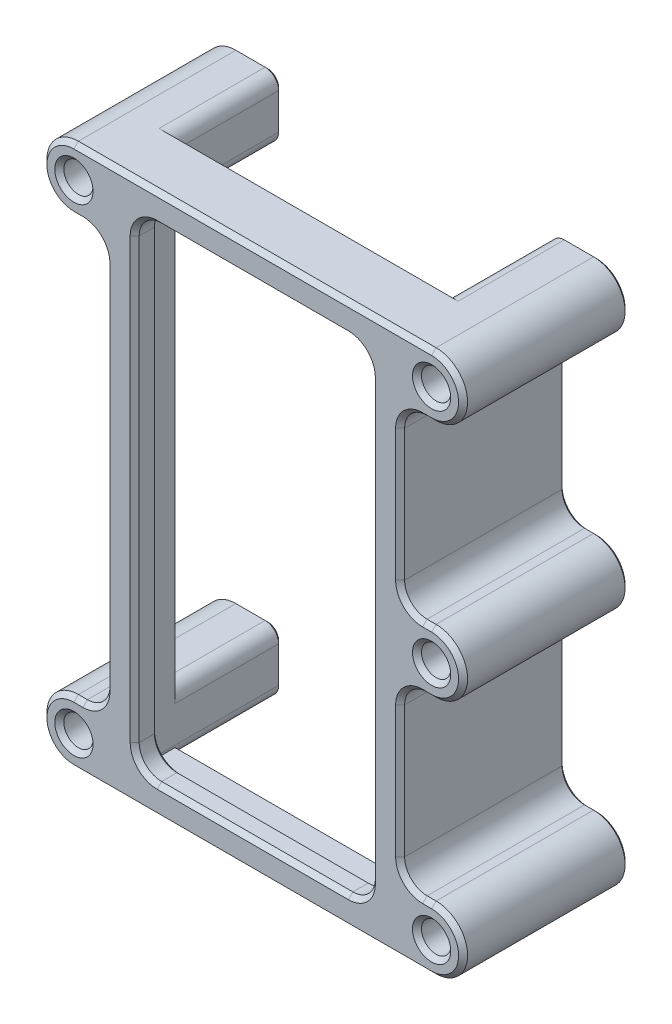
SolidWorks part; units mm, degrees
ref_plane "Top Plane" through (0, 0, 0) normal (0, 0, 1) x (1, 0, 0)
ref_plane "Right Plane" through (0, 0, 0) normal (0, 1, 0) x (1, 0, 0)
ref_plane "Front Plane" through (0, 0, 0) normal (1, 0, 0) x (0, 0, -1)
sketch "Sketch1" plane through (0, 0, 0) normal (0, 0, 1) x (1, 0, 0)
  line L0 (60.25, -113.75) -> (60.25, -1.25) construction
  line L1 (-0.25, -115.25) -> (60.25, -115.25)
  line L2 (-0.25, -115.25) -> (-0.25, 0.25)
  line L3 (-0.25, 0.25) -> (60.25, 0.25)
  line L4 (60.25, -115.25) -> (60.25, 0.25)
  line L5 (60.25, 0.25) -> (36.1, 0.25) construction
  line L6 (-0.25, -115.25) -> (22.5, -115.25) construction
  line L7 (-0.25, -113.75) -> (-0.25, -58) construction
  line L8 (36, 2.75) -> (69.75, 2.75) construction
  line L10 (-2.75, -103.75) -> (-2.75, -11.25)
  line L11 (-9.75, 2.75) -> (69.75, 2.75)
  line L14 (-2.75, -98.75) -> (-2.75, -71.862) construction
  line L16 (-9.75, -117.75) -> (69.75, -117.75)
  line L17 (-9.75, -103.75) -> (-2.75, -103.75)
  line L18 (69.75, -103.75) -> (62.75, -103.75)
  line L19 (69.75, -64.5) -> (62.75, -64.5)
  line L20 (69.75, -50.5) -> (62.75, -50.5)
  line L21 (69.75, -11.25) -> (62.75, -11.25)
  line L22 (-9.75, -11.25) -> (-2.75, -11.25)
  line L23 (62.75, -103.75) -> (62.75, -64.5)
  line L24 (62.75, -50.5) -> (62.75, -11.25)
  line L25 (62.75, -69.5) -> (62.75, -98.75) construction
  arc A0 (69.75, -64.5) -> (69.75, -50.5) centre (69.75, -57.5) ccw
  arc A1 (69.75, -11.25) -> (69.75, 2.75) centre (69.75, -4.25) ccw
  arc A2 (69.75, -117.75) -> (69.75, -103.75) centre (69.75, -110.75) ccw
  arc A3 (-9.75, -103.75) -> (-9.75, -117.75) centre (-9.75, -110.75) ccw
  arc A4 (-9.75, 2.75) -> (-9.75, -11.25) centre (-9.75, -4.25) ccw
  arc A5 (-9.75, -103.75) -> (-9.75, -117.75) centre (-9.75, -110.75) ccw construction
  circle A7 centre (-9.75, -110.75) radius 3.25
  circle A8 centre (-9.75, -4.25) radius 3.25
  circle A9 centre (69.75, -4.25) radius 3.25
  circle A10 centre (69.75, -57.5) radius 3.25
  circle A11 centre (69.75, -110.75) radius 3.25
  dimension "D1" = 6.5
extrude "Boss-Extrude1" add sketch "Sketch1" along normal blind 5 and the other way blind 8 contours L11 A4 L22 L10 L17 A3 L16 A2 L18 L23 L19 A0 L20 L24 L21 A1 A11 A10 A9 A8 A7 L4 L1 L2 L3 region at (-1.2248, -57.5, 0)
sketch "Sketch2" plane through (0, 0, 0) normal (0, 0, 1) x (1, 0, 0)
  line L4 (-0.25, -115.25) -> (60.25, -115.25) construction
  line L5 (60.25, -115.25) -> (60.25, 0.25) construction
  line L6 (-0.25, 0.25) -> (60.25, 0.25) construction
  line L7 (-0.25, -115.25) -> (-0.25, 0.25) construction
  line L8 (3.75, -111.25) -> (56.25, -111.25)
  line L9 (56.25, -111.25) -> (56.25, -3.75)
  line L10 (3.75, -3.75) -> (3.75, -111.25)
  line L11 (56.25, -3.75) -> (3.75, -3.75)
  line L12 (3.75, -111.25) -> (56.25, -111.25)
  line L13 (56.25, -111.25) -> (56.25, -3.75)
  line L14 (3.75, -3.75) -> (3.75, -111.25)
  line L15 (56.25, -3.75) -> (3.75, -3.75)
  line L16 (-0.25, -115.25) -> (60.25, -115.25)
  line L17 (60.25, -115.25) -> (60.25, 0.25)
  line L18 (-0.25, 0.25) -> (60.25, 0.25)
  line L19 (-0.25, -115.25) -> (-0.25, 0.25)
  dimension "D1" = 4
extrude "Boss-Extrude2" add sketch "Sketch2" along normal up to surface (5 mm away) contours L19 L16 L17 L18 L15 L13 L12 L14 region at (1.0539, -57.5, 0) up to face at (73, -110.75, 5)
sketch "Sketch3" plane through (0, 0, -8) normal (0, 0, -1) x (-1, 0, 0)
  line L1 (0.25, -115.25) -> (0.25, 0.25) construction
  line L3 (-60.25, -115.25) -> (-60.25, 0.25) construction
  line L5 (0.25, -117.75) -> (0.25, -103.75)
  line L7 (-60.25, -117.75) -> (-60.25, 2.75)
  line L8 (0.25, -11.25) -> (0.25, 2.75)
  line L9 (-60.25, 2.75) -> (-69.75, 2.75)
  line L10 (0.25, -117.75) -> (9.75, -117.75)
  line L11 (9.75, 2.75) -> (-69.75, 2.75)
  line L12 (-69.75, -11.25) -> (-62.75, -11.25)
  line L13 (-62.75, -11.25) -> (-62.75, -50.5)
  line L14 (-62.75, -50.5) -> (-69.75, -50.5)
  line L15 (-69.75, -64.5) -> (-62.75, -64.5)
  line L16 (-62.75, -64.5) -> (-62.75, -103.75)
  line L17 (-62.75, -103.75) -> (-69.75, -103.75)
  line L18 (-69.75, -117.75) -> (9.75, -117.75)
  line L19 (9.75, -103.75) -> (2.75, -103.75)
  line L20 (2.75, -103.75) -> (2.75, -11.25)
  line L21 (2.75, -11.25) -> (9.75, -11.25)
  line L22 (9.75, 2.75) -> (0.25, 2.75)
  line L23 (-69.75, -11.25) -> (-62.75, -11.25)
  line L24 (-62.75, -11.25) -> (-62.75, -50.5)
  line L25 (-62.75, -50.5) -> (-69.75, -50.5)
  line L26 (-69.75, -64.5) -> (-62.75, -64.5)
  line L27 (-62.75, -64.5) -> (-62.75, -103.75)
  line L28 (-62.75, -103.75) -> (-69.75, -103.75)
  line L29 (-69.75, -117.75) -> (-60.25, -117.75)
  line L30 (9.75, -103.75) -> (0.25, -103.75)
  line L32 (0.25, -11.25) -> (9.75, -11.25)
  arc A5 (-69.75, 2.75) -> (-69.75, -11.25) centre (-69.75, -4.25) ccw
  arc A6 (-69.75, -50.5) -> (-69.75, -64.5) centre (-69.75, -57.5) ccw
  arc A7 (-69.75, -103.75) -> (-69.75, -117.75) centre (-69.75, -110.75) ccw
  arc A8 (9.75, -117.75) -> (9.75, -103.75) centre (9.75, -110.75) ccw
  arc A9 (9.75, -11.25) -> (9.75, 2.75) centre (9.75, -4.25) ccw
  arc A10 (-69.75, 2.75) -> (-69.75, -11.25) centre (-69.75, -4.25) ccw
  arc A11 (-69.75, -50.5) -> (-69.75, -64.5) centre (-69.75, -57.5) ccw
  arc A12 (-69.75, -103.75) -> (-69.75, -117.75) centre (-69.75, -110.75) ccw
  arc A13 (9.75, -117.75) -> (9.75, -103.75) centre (9.75, -110.75) ccw
  arc A14 (9.75, -11.25) -> (9.75, 2.75) centre (9.75, -4.25) ccw
  circle M22 centre (-69.75, -110.75) radius 3.25
  circle M23 centre (-69.75, -57.5) radius 3.25
  circle M24 centre (-69.75, -4.25) radius 3.25
  circle M25 centre (9.75, -4.25) radius 3.25
  circle M26 centre (9.75, -110.75) radius 3.25
  line M27 (-60.25, -115.25) -> (-60.25, 0.25)
  line M29 (0.25, 0.25) -> (0.25, -115.25)
  line M31 (9.75, 2.75) -> (-69.75, 2.75)
  arc M32 (-69.75, 2.75) -> (-69.75, -11.25) centre (-69.75, -4.25) ccw
  line M33 (-69.75, -11.25) -> (-62.75, -11.25)
  line M34 (-62.75, -11.25) -> (-62.75, -50.5)
  line M35 (-62.75, -50.5) -> (-69.75, -50.5)
  arc M36 (-69.75, -50.5) -> (-69.75, -64.5) centre (-69.75, -57.5) ccw
  line M37 (-69.75, -64.5) -> (-62.75, -64.5)
  line M38 (-62.75, -64.5) -> (-62.75, -103.75)
  line M39 (-62.75, -103.75) -> (-69.75, -103.75)
  arc M40 (-69.75, -103.75) -> (-69.75, -117.75) centre (-69.75, -110.75) ccw
  line M41 (-69.75, -117.75) -> (9.75, -117.75)
  arc M42 (9.75, -117.75) -> (9.75, -103.75) centre (9.75, -110.75) ccw
  line M43 (9.75, -103.75) -> (2.75, -103.75)
  line M45 (2.75, -11.25) -> (9.75, -11.25)
  arc M46 (9.75, -11.25) -> (9.75, 2.75) centre (9.75, -4.25) ccw
  dimension "D1" = 0
extrude "Boss-Extrude3" add sketch "Sketch3" along normal up to surface (23.6 mm away) contours L7 M41 M27 M31 M32 M33 M34 M35 M36 M37 M38 M39 M40 M22 M24 M23 | L32 L8 M29 M45 M46 M31 M25 | L30 L5 M43 M29 M41 M42 M26 region at (-0.4664, -116.5, -8) region at (65.8575, -57.5, -8) region at (-0.4664, -5.5, -8)
fillet "Fillet1" radius 5 6 edges at (62.75, -11.25, -13.3) (62.75, -103.75, -13.3) (-2.75, -103.75, -1.5) (62.75, -64.5, -13.3) (62.75, -50.5, -13.3) (-2.75, -11.25, -1.5)
fillet "Fillet2" radius 5 4 edges at (3.75, -3.75, 2.5) (56.25, -3.75, 2.5) (56.25, -111.25, 2.5) (3.75, -111.25, 2.5)
sketch "Sketch4" plane through (0, 0, -31.6) normal (0, 0, -1) x (-1, 0, 0)
  circle A0 centre (-69.75, -4.25) radius 1.9
  circle A1 centre (-69.75, -57.5) radius 1.9
  circle A2 centre (-69.75, -110.75) radius 1.9
  circle A3 centre (9.75, -110.75) radius 1.9
  circle A4 centre (9.75, -4.25) radius 1.9
  circle A5 centre (9.75, -110.75) radius 3.25 construction
  circle A6 centre (-69.75, -110.75) radius 3.25 construction
  circle A7 centre (-69.75, -57.5) radius 3.25 construction
  circle A8 centre (9.75, -4.25) radius 3.25 construction
  circle A9 centre (-69.75, -4.25) radius 3.25 construction
  circle A10 centre (9.75, -110.75) radius 3.25
  circle A11 centre (-69.75, -110.75) radius 3.25
  circle A12 centre (-69.75, -57.5) radius 3.25
  circle A13 centre (9.75, -4.25) radius 3.25
  circle A14 centre (-69.75, -4.25) radius 3.25
  circle M3 centre (-69.75, -4.25) radius 3.25
  circle M20 centre (-69.75, -110.75) radius 3.25
  circle M21 centre (-69.75, -57.5) radius 3.25
  dimension "D1" = 3.8
extrude "Boss-Extrude4" add sketch "Sketch4" against normal blind 12 contours A0 M3 | A13 A4 | A10 A3 | A2 M20 | A1 M21 region at (-6.5919, -110.75, -31.6) region at (72.9081, -110.75, -31.6) region at (72.9081, -57.5, -31.6) region at (-6.5919, -4.25, -31.6) region at (72.9081, -4.25, -31.6)
fillet "Fillet3" radius 3 6 edges at (-0.25, -103.75, -19.8) (-0.25, -11.25, -19.8) (-0.25, -117.75, -19.8) (60.25, -117.75, -19.8) (60.25, 2.75, -19.8) (-0.25, 2.75, -19.8)
chamfer "Chamfer1" distance 0.6 angle 45 30 edges at (-1.1287, -10.3713, -31.6) (-0.25, -4.25, -31.6) (-6.5, -11.25, -31.6) (-1.1287, 1.8713, -31.6) (-16.75, -4.25, -31.6) (-6.5, 2.75, -31.6) (-0.25, -110.75, -31.6) (-1.1287, -116.8713, -31.6) (-1.1287, -104.6287, -31.6) (-6.5, -117.75, -31.6) (-6.5, -103.75, -31.6) (-16.75, -110.75, -31.6) (66.5, -117.75, -31.6) (61.1287, -116.8713, -31.6) (76.75, -110.75, -31.6) (60.25, -57.5, -31.6) (68.75, -103.75, -31.6) (61.1287, 1.8713, -31.6) (64.2145, -102.2855, -31.6) (66.5, 2.75, -31.6) (62.75, -84.125, -31.6) (76.75, -4.25, -31.6) (64.2145, -65.9645, -31.6) (68.75, -11.25, -31.6) (68.75, -64.5, -31.6) (64.2145, -12.7145, -31.6) (76.75, -57.5, -31.6) (62.75, -30.875, -31.6) (68.75, -50.5, -31.6) (64.2145, -49.0355, -31.6)
chamfer "Chamfer2" distance 0.6 angle 45 10 edges at (-11.65, -4.25, -31.6) (67.85, -4.25, -31.6) (67.85, -57.5, -31.6) (67.85, -110.75, -31.6) (-11.65, -110.75, -31.6) (-4.2145, -102.2855, -8) (-4.2145, -12.7145, -8) (-2.75, -57.5, -8) (30, -117.75, -8) (30, 2.75, -8)
chamfer "Chamfer3" distance 1 angle 45 35 edges at (5.2145, -109.7855, 5) (3.75, -57.5, 5) (30, -111.25, 5) (5.2145, -5.2145, 5) (54.7855, -109.7855, 5) (30, -3.75, 5) (56.25, -57.5, 5) (54.7855, -5.2145, 5) (73, -4.25, 5) (73, -57.5, 5) (73, -110.75, 5) (-6.5, -110.75, 5) (64.2145, -102.2855, 5) (68.75, -103.75, 5) (62.75, -84.125, 5) (76.75, -110.75, 5) (64.2145, -65.9645, 5) (30, -117.75, 5) (68.75, -64.5, 5) (-16.75, -110.75, 5) (76.75, -57.5, 5) (-8.75, -103.75, 5) (68.75, -50.5, 5) (-4.2145, -102.2855, 5) (64.2145, -49.0355, 5) (-2.75, -57.5, 5) (62.75, -30.875, 5) (-4.2145, -12.7145, 5) (64.2145, -12.7145, 5) (-8.75, -11.25, 5) (68.75, -11.25, 5) (-16.75, -4.25, 5) (76.75, -4.25, 5) (30, 2.75, 5) (-6.5, -4.25, 5)
chamfer "Chamfer4" distance 0.6 angle 45 8 edges at (56.25, -57.5, 0) (54.7855, -5.2145, 0) (54.7855, -109.7855, 0) (30, -3.75, 0) (30, -111.25, 0) (5.2145, -5.2145, 0) (5.2145, -109.7855, 0) (3.75, -57.5, 0)
chamfer "Chamfer5" distance 1.5 angle 45 5 edges at (67.85, -110.75, -19.6) (67.85, -57.5, -19.6) (67.85, -4.25, -19.6) (-11.65, -4.25, -19.6) (-11.65, -110.75, -19.6)
